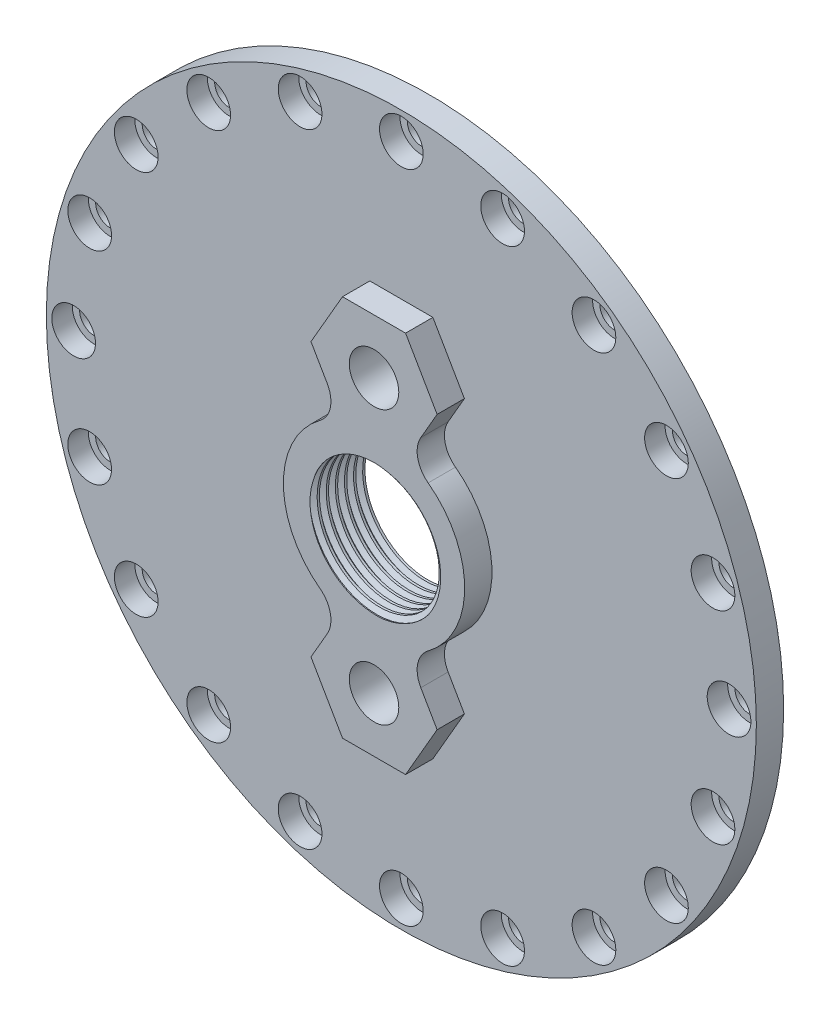
SolidWorks part; units mm, degrees
ref_plane "Front Plane" through (0, 0, 0) normal (0, 0, 1) x (1, 0, 0)
ref_plane "Top Plane" through (0, 0, 0) normal (0, 1, 0) x (1, 0, 0)
ref_plane "Right Plane" through (0, 0, 0) normal (1, 0, 0) x (0, 0, -1)
sketch "Sketch1" plane through (0, 0, 0) normal (1, 0, 0) x (0, 0, -1)
  line L0 (0, 21.082) -> (0, 82.55)
  line L1 (0, 82.55) -> (6.35, 82.55)
  line L2 (6.35, 82.55) -> (6.35, 63.5)
  line L3 (6.35, 63.5) -> (3.81, 63.5)
  line L4 (3.81, 63.5) -> (3.81, 42.545)
  line L5 (3.81, 42.545) -> (6.35, 42.545)
  line L6 (6.35, 42.545) -> (6.35, 41.275)
  line L7 (6.35, 14.732) -> (-6.35, 14.732)
  line L8 (-6.35, 14.732) -> (-6.35, 21.082)
  line L9 (-6.35, 21.082) -> (0, 21.082)
  line L10 (0, 0) -> (59.2702, 0) construction
  line L12 (6.35, 41.275) -> (5.08, 41.275)
  line L14 (6.35, 40.005) -> (5.08, 40.005)
  line L15 (5.08, 41.275) -> (5.08, 40.005)
  line L20 (6.35, 40.005) -> (6.35, 14.732)
  point P22 (5.08, 40.64)
  dimension "D1" = 165.1
  dimension "D2" = 2.54
  dimension "D3" = 6.35
  dimension "D4" = 127
  dimension "D5" = 85.09
  dimension "D6" = 12.7
  dimension "D7" = 29.464
  dimension "D8" = 6.35
  dimension "D9" = 1.27
  dimension "D10" = 81.28
  dimension "D11" = 1.27
revolve "Revolve1" add sketch "Sketch1" angle 360 about L10
thread "Thread1" pitch 2.1167 method cut profile "Thread Profile1" start angle 0, offset 4.318, length 0, pitch 2.1167, diameter 29.464
ref_plane "Plane1" through (-14.732, 0, 10.668) normal (0, -1, 0) x (-1, 0, 0)
sketch "Thread Profile1" plane through (-14.732, 0, 10.668) normal (0, -1, 0) x (-1, 0, 0)
  line L0 (0, 0) -> (0, 2.1167) construction
  line L1 (0, 0) -> (1.1457, 0.6615)
  line L2 (1.1457, 0.6615) -> (1.1457, 0.926)
  line L3 (1.1457, 0.926) -> (0, 1.5875)
  line L4 (1.1457, 0.7937) -> (0, 0.7937) construction
  line L11 (0, 0) -> (0, 1.5875)
  point P2 (0, 0)
  dimension "Pitch" = 2.1167
  dimension "Profile_Angle" = 60
  dimension "Profile_Land" = 0.2646
  dimension "Profile_Height" = 1.1457
sketch "Sketch15" plane through (0, 0, 0) normal (0, 0, 1) x (1, 0, 0)
  line L10 (0, 0) -> (104.8126, 0) construction
  line L11 (7.3323, 19.05) -> (14.6647, 31.75)
  line L12 (14.6647, 31.75) -> (7.3323, 44.45)
  line L13 (7.3323, 44.45) -> (-7.3323, 44.45)
  line L14 (-7.3323, 44.45) -> (-14.6647, 31.75)
  line L15 (-14.6647, 31.75) -> (-7.3323, 19.05)
  line L16 (-7.3323, 19.05) -> (7.3323, 19.05)
  line L17 (-7.3323, -19.05) -> (7.3323, -19.05)
  line L18 (-14.6647, -31.75) -> (-7.3323, -19.05)
  line L19 (-7.3323, -44.45) -> (-14.6647, -31.75)
  line L20 (7.3323, -44.45) -> (-7.3323, -44.45)
  line L21 (14.6647, -31.75) -> (7.3323, -44.45)
  line L22 (7.3323, -19.05) -> (14.6647, -31.75)
  circle A8 centre (0, 31.75) radius 12.7 construction
  circle A9 centre (0, -31.75) radius 12.7 construction
  dimension "D2" = 63.5
  dimension "D1" = 25.4
extrude "Boss-Extrude1" add sketch "Sketch15" along normal up to surface (6.35 mm away) up to face at (21.082, 0, 6.35)
hole_wizard "1/2-20 Tapped Hole2" positions "Sketch18" profile "Sketch17" tap size "1/2-20" standard "ANSI Inch" end condition up to next
sketch "Sketch18" plane through (0, 0, 6.35) normal (0, 0, 1) x (1, 0, 0)
  point P9 (0, 31.75)
  point P16 (0, -31.75)
sketch "Sketch17" plane through (0, 31.75, 6.35) normal (1, 0, 0) x (0, -1, 0)
  line L0 (0, 0) -> (0, 12.7)
  line L1 (0, 12.7) -> (5.7544, 12.7)
  line L2 (5.7544, 12.7) -> (5.7544, 0)
  line L5 (5.7544, 0) -> (0, 0)
  line L11 (0, -6.35) -> (0, 107.95) construction
  dimension "Thru Tap Drill Dia." = 11.5087
  dimension "Thru Tap Drill Depth" = 12.7
cosmetic thread "Hole Thread3"
cosmetic thread "Hole Thread4"
hole_wizard "CBORE for 1/4 Socket Head Cap Screw1" positions "Sketch12" profile "Sketch9" counterbore size "1/4" standard "ANSI Inch" end condition up to next
sketch "Sketch12" plane through (0, 0, 0) normal (0, 0, 1) x (1, 0, 0)
  circle A0 centre (0, 0) radius 76.2 construction
  point P0 (0, 76.2)
  point P16 (23.5471, 72.4705)
  point P17 (44.7892, 61.6471)
  point P18 (61.6471, 44.7892)
  point P19 (72.4705, 23.5471)
  point P20 (76.2, 0)
  point P21 (72.4705, -23.5471)
  point P22 (61.6471, -44.7892)
  point P23 (44.7892, -61.6471)
  point P24 (23.5471, -72.4705)
  point P25 (0, -76.2)
  point P26 (-23.5471, -72.4705)
  point P27 (-44.7892, -61.6471)
  point P28 (-61.6471, -44.7892)
  point P29 (-72.4705, -23.5471)
  point P30 (-76.2, 0)
  point P31 (-72.4705, 23.5471)
  point P32 (-61.6471, 44.7892)
  point P33 (-44.7892, 61.6471)
  point P34 (-23.5471, 72.4705)
  dimension "D1" = 152.4
  dimension "D2" = 20
sketch "Sketch9" plane through (0, 76.2, 0) normal (1, 0, 0) x (0, -1, 0)
  line L0 (0, 0) -> (0, 6.35)
  line L1 (0, 6.35) -> (3.3782, 6.35)
  line L3 (3.3782, 6.35) -> (3.3782, 4.7625)
  line L4 (3.3782, 4.7625) -> (5.08, 4.7625)
  line L5 (5.08, 4.7625) -> (5.08, 0)
  line L7 (5.08, 0) -> (0, 0)
  line L11 (0, -6.35) -> (0, 107.95) construction
  dimension "Thru Hole Dia." = 6.7564
  dimension "Thru Hole Depth" = 6.35
  dimension "C'Bore Dia." = 10.16
  dimension "C'Bore Depth" = 4.7625
fillet "Fillet1" radius 6.35 4 edges at (-7.6711, 19.6368, 3.175) (-7.6711, -19.6368, 3.175) (7.6711, -19.6368, 3.175) (7.6711, 19.6368, 3.175)
